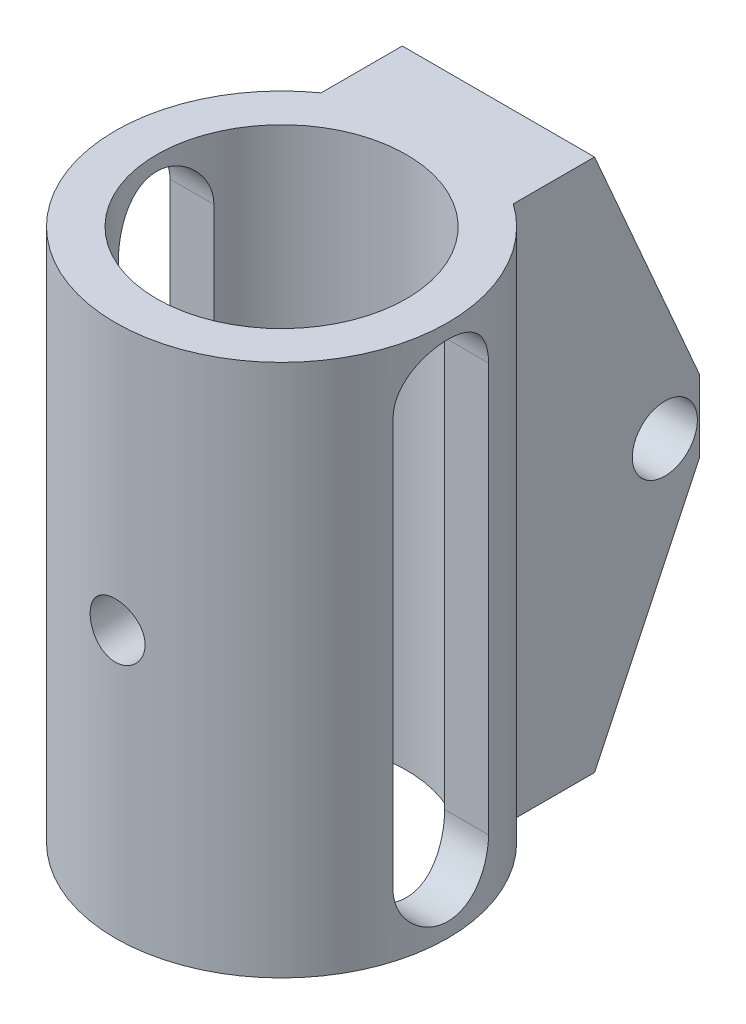
SolidWorks part; units mm, degrees
ref_plane "Front Plane" through (0, 0, 0) normal (0, 0, 1) x (1, 0, 0)
ref_plane "Top Plane" through (0, 0, 0) normal (0, 1, 0) x (1, 0, 0)
ref_plane "Right Plane" through (0, 0, 0) normal (1, 0, 0) x (0, 0, -1)
sketch "Sketch1" plane through (0, 0, 0) normal (0, 1, 0) x (1, 0, 0)
  circle A0 centre (0, 0) radius 8.6383
  circle A1 centre (0, 0) radius 11.5
  dimension "D1" = 17.2766
  dimension "D2" = 23
extrude "Boss-Extrude1" add sketch "Sketch1" along normal blind 36.88
ref_plane "Plane1" through (-11.5, 0, 0) normal (-1, 0, 0) x (0, 0, 1)
sketch "Sketch2" plane through (-11.5, 0, 0) normal (-1, 0, 0) x (0, 0, 1)
  line L0 (0, 32.5733) -> (0, 4.3067) construction
  line L1 (3.302, 32.5733) -> (3.302, 4.3067)
  line L2 (-3.302, 32.5733) -> (-3.302, 4.3067)
  line L3 (0, 32.5733) -> (0, 36.88) construction
  line L4 (8.6383, 36.88) -> (-8.6383, 36.88) construction
  line L5 (0, 4.3067) -> (0, 0) construction
  arc A0 (3.302, 32.5733) -> (-3.302, 32.5733) centre (0, 32.5733) ccw
  arc A1 (-3.302, 4.3067) -> (3.302, 4.3067) centre (0, 4.3067) ccw
  point P3 (0, 18.44)
  dimension "D1" = 3.302
extrude "Cut-Extrude1" cut sketch "Sketch2" against normal blind 55.88
sketch "Sketch3" plane through (0, 0, 0) normal (0, 0, 1) x (1, 0, 0)
  line L0 (0, 36.88) -> (0, 18.44) construction
  line L1 (11.5, 36.88) -> (-11.5, 36.88) construction
  circle A0 centre (0, 18.44) radius 1.9
  dimension "D1" = 3.8
  dimension "D2" = 18.44
extrude "Cut-Extrude2" cut sketch "Sketch3" along normal through all
sketch "Sketch4" plane through (0, 0, 0) normal (0, 0, 1) x (1, 0, 0)
  line L0 (-8.6383, 0) -> (-6.6495, 0) construction
  line L5 (8.6383, 0) -> (6.6495, 0) construction
  line L6 (8.6383, 36.88) -> (6.6495, 36.88) construction
  line L7 (-8.6383, 36.88) -> (-6.6495, 36.88) construction
  line L9 (6.6495, 0) -> (-6.6495, 0)
  line L10 (6.6495, 0) -> (6.6495, 36.88)
  line L11 (6.6495, 36.88) -> (-6.6495, 36.88)
  line L12 (-6.6495, 0) -> (-6.6495, 36.88)
extrude "Boss-Extrude2" add sketch "Sketch4" along normal up to surface (5.6174 mm away) from offset 15 up to face at (11.2557, 18.44, 0) offset against normal yes
sketch "Sketch5" plane through (-6.6495, 0, 0) normal (-1, 0, 0) x (0, 0, 1)
  line L0 (-22.264, 15.2344) -> (-22.264, 20.2202)
  line L1 (-15, 36.88) -> (-22.264, 20.2202)
  line L2 (-22.264, 15.2344) -> (-15, 0)
  line L3 (-15, 17.577) -> (-19.8654, 17.577) construction
  line L4 (-15, 36.88) -> (-15, 0) construction
  circle A0 centre (-19.8654, 17.577) radius 2.25
  point P6 (-22.2657, 17.577)
  line M4 (-15, 36.88) -> (-15, 0)
  dimension "D1" = 4.5
extrude "Boss-Extrude3" add sketch "Sketch5" along direction (-1, 0, 0) on the side against the normal up to surface (13.299 mm away) contours L0 L2 L1 A0 M4 region at (-6.6495, 18.2439, -17.4579) up to face at (6.6495, 18.44, -12.1913)
